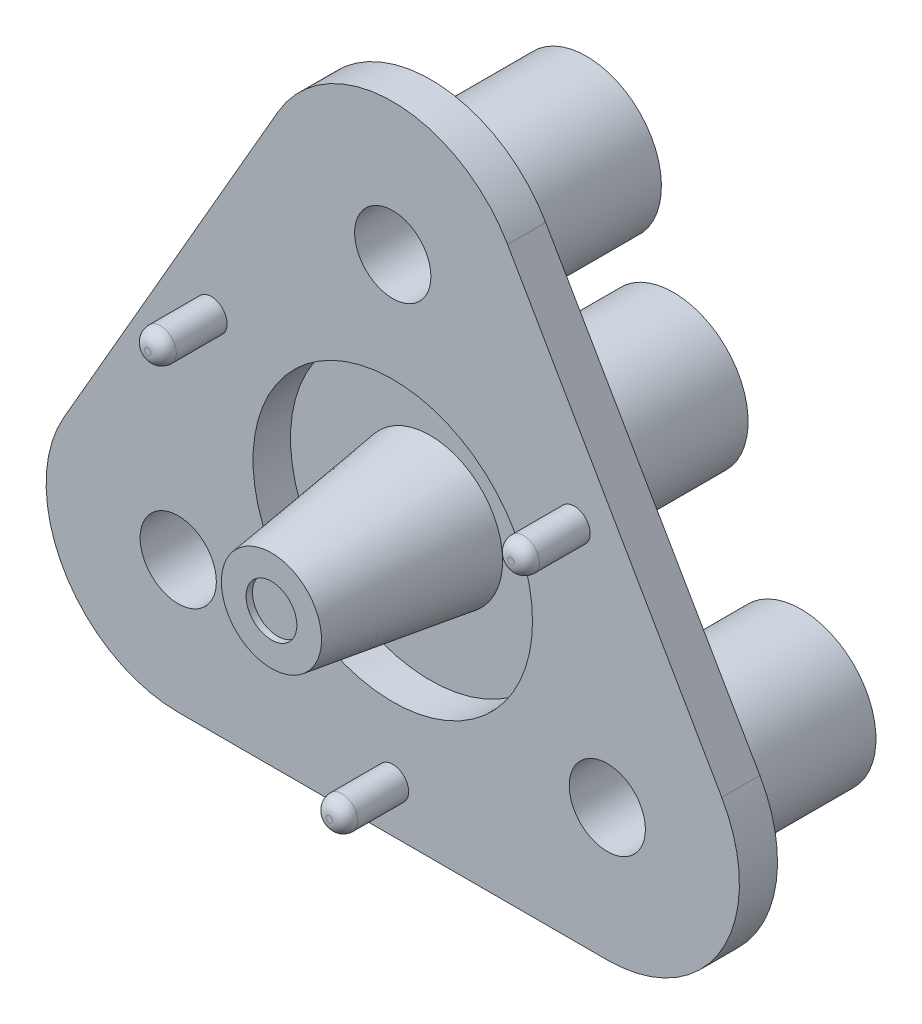
SolidWorks part; units mm, degrees
ref_plane "Front Plane" through (0, 0, 0) normal (0, 0, 1) x (1, 0, 0)
ref_plane "Top Plane" through (0, 0, 0) normal (0, 1, 0) x (1, 0, 0)
ref_plane "Right Plane" through (0, 0, 0) normal (1, 0, 0) x (0, 0, -1)
sketch "Sketch1" plane through (0, 0, 0) normal (0, 0, 1) x (1, 0, 0)
  line L0 (0, 0) -> (0, -9.7536) construction
  line L1 (0, -13.7185) -> (0, 13.7185) construction
  line L2 (0, 0) -> (0, 15.205) construction
  line L3 (0, 0) -> (8.4469, 4.8768) construction
  line L4 (0, 0) -> (-13.1542, -7.5946) construction
  line L5 (0, 0) -> (-8.4469, 4.8768) construction
  line L6 (0, 0) -> (13.1542, -7.5946) construction
  line L7 (0, 0) -> (0, 9.906) construction
  line L8 (0, 0) -> (8.5788, -4.953) construction
  line L9 (0, 0) -> (-8.5788, -4.953) construction
  line L10 (-4.5915, 12.5513) -> (-13.1567, -2.3156)
  line L11 (4.5915, 12.5513) -> (13.1567, -2.3156)
  line L12 (-8.5788, -10.2362) -> (8.5788, -10.2362)
  circle A0 centre (-8.5788, -4.953) radius 5.2832 construction
  circle A1 centre (0, 9.906) radius 5.299 construction
  circle A2 centre (8.5788, -4.953) radius 5.2832 construction
  arc A3 (-4.5915, 12.5513) -> (4.5915, 12.5513) centre (0, 9.906) cw
  arc A4 (8.5788, -10.2362) -> (13.1567, -2.3156) centre (8.5788, -4.953) ccw
  arc A5 (-8.5788, -10.2362) -> (-13.1567, -2.3156) centre (-8.5788, -4.953) cw
extrude "Boss-Extrude1" add sketch "Sketch1" along normal blind 1.524
sketch "Sketch2" plane through (0, 0, 1.524) normal (0, 0, 1) x (1, 0, 0)
  circle A0 centre (0, 0) radius 5.588
extrude "Cut-Extrude1" cut sketch "Sketch2" against normal blind 1.4986
sketch "Sketch3" plane through (0, 0, 0.0254) normal (0, 0, 1) x (1, 0, 0)
  circle A0 centre (0, 0) radius 2.8956
extrude "Boss-Extrude2" add sketch "Sketch3" along normal blind 6.35
chamfer "Chamfer1" distance 6.35 angle 8 1 edges at (2.8956, 0, 6.3754) first distance on face at (2.8956, 0, 6.3754)
sketch "Sketch4" plane through (0, 0, 6.3754) normal (0, 0, 1) x (1, 0, 0)
  circle A0 centre (0, 0) radius 1.016
extrude "Cut-Extrude2" cut sketch "Sketch4" against normal blind 0.254
sketch "Sketch5" plane through (0, 0, 0) normal (0, 0, -1) x (-1, 0, 0)
  circle A0 centre (0, 0) radius 7.366
extrude "Boss-Extrude3" add sketch "Sketch5" along normal blind 1.778
sketch "Sketch6" plane through (0, 0, 0) normal (0, 0, -1) x (-1, 0, 0)
  arc A0 (-1.3661, 7.2382) -> (1.3661, 7.2382) centre (0, 9.906) cw
  circle A1 centre (0, 0) radius 7.366 construction
  arc A2 (1.3661, 7.2382) -> (-1.3661, 7.2382) centre (0, 0) ccw
extrude "Boss-Extrude4" add sketch "Sketch6" along normal blind 1.778
pattern_circular "CirPattern1" count 3 every 120 about axis through (0, 0, -1.778) along (0, 0, -1) of "Boss-Extrude4"
sketch "Sketch7" plane through (0, 0, -1.778) normal (0, 0, -1) x (-1, 0, 0)
  circle A0 centre (0, 9.906) radius 2.9972
extrude "Boss-Extrude5" add sketch "Sketch7" along normal blind 4.445
pattern_circular "CirPattern2" count 3 every 120 about axis through (0, 0, -1.778) along (0, 0, -1) of "Boss-Extrude5"
sketch "Sketch8" plane through (0, 0, -6.223) normal (0, 0, -1) x (-1, 0, 0)
  circle A0 centre (8.5788, -4.953) radius 1.4859
extrude "Cut-Extrude3" cut sketch "Sketch8" against normal blind 0.0508
pattern_circular "CirPattern3" count 3 every 120 about axis through (0, 0, -1.778) along (0, 0, -1) of "Cut-Extrude3"
sketch "Sketch9" plane through (0, 0, -1.778) normal (0, 0, -1) x (-1, 0, 0)
  circle A0 centre (0, 0) radius 2.9845
extrude "Boss-Extrude6" add sketch "Sketch9" along normal blind 7.9248
sketch "Sketch10" plane through (0, 0, -9.7028) normal (0, 0, -1) x (-1, 0, 0)
  line L1 (-1.4665, 0) -> (-0.7332, -1.27)
  line L2 (-0.7332, -1.27) -> (0.7332, -1.27)
  line L3 (0.7332, -1.27) -> (1.4665, 0)
  line L4 (1.4665, 0) -> (0.7332, 1.27)
  line L5 (0.7332, 1.27) -> (-0.7332, 1.27)
  line L6 (-0.7332, 1.27) -> (-1.4665, 0)
  circle A0 centre (0, 0) radius 1.27 construction
extrude "Cut-Extrude4" cut sketch "Sketch10" against normal blind 14.732
sketch "Sketch11" plane through (0, 0, -9.7028) normal (0, 0, -1) x (-1, 0, 0)
  circle A0 centre (0, 0) radius 1.524
extrude "Cut-Extrude5" cut sketch "Sketch11" against normal blind 3.81
ref_point "Point1"
sketch "Sketch16" plane through (0, 0, 1.524) normal (0, 0, 1) x (1, 0, 0)
  circle A0 centre (-8.5788, -4.953) radius 1.524
extrude "Cut-Extrude6" cut sketch "Sketch16" against normal blind 6.35
pattern_circular "CirPattern4" count 3 every 120 about axis through (0, 0, 0.0254) along (0, 0, 1) of "Cut-Extrude6"
sketch "Sketch17" plane through (0, 0, 1.524) normal (0, 0, 1) x (1, 0, 0)
  line L0 (0, 0) -> (0, -8.382) construction
  line L1 (0, -13.7185) -> (0, 13.7185) construction
  circle A0 centre (0, -8.382) radius 0.635
extrude "Boss-Extrude7" add sketch "Sketch17" along normal blind 2.54
fillet "Fillet1" radius 0.508 1 edges at (0.635, -8.382, 4.064)
pattern_circular "CirPattern6" count 3 every 120 about axis through (0, 0, 0.0254) along (0, 0, 1) of "Fillet1", "Boss-Extrude7"
